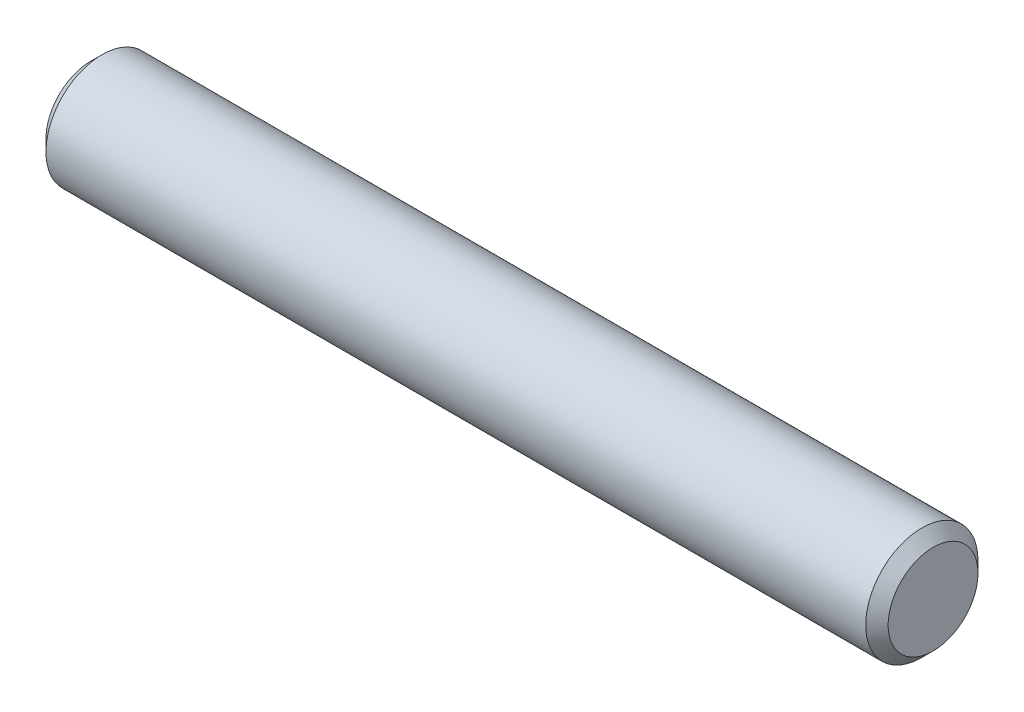
SolidWorks part; units mm, degrees
ref_plane "Front" through (0, 0, 0) normal (0, 0, 1) x (1, 0, 0)
ref_plane "Top" through (0, 0, 0) normal (0, 1, 0) x (1, 0, 0)
ref_plane "Right" through (0, 0, 0) normal (1, 0, 0) x (0, 0, -1)
sketch "Sketch1" plane through (0, 0, 0) normal (0, 0, 1) x (1, 0, 0)
  line L0 (-23.8125, 0) -> (23.8125, 0) construction
  line L1 (23.8125, 3.175) -> (23.8125, -3.175) construction
  line L2 (-23.8125, 3.175) -> (-23.8125, -3.175) construction
sketch "Sketch2" plane through (0, 0, 0) normal (1, 0, 0) x (0, 0, -1)
  line L0 (3.175, 0) -> (-3.175, 0) construction
  circle A0 centre (0, 0) radius 3.175
  point P6 (0, 0)
  dimension "D1" = 6.35
extrude "Extrude1" add sketch "Sketch2" against normal up to vertex (23.8125 mm away) and the other way up to vertex (23.8125 mm away) up to point (-23.8125, 3.175, 0) other way up to point (23.8125, 3.175, 0)
chamfer "Chamfer1" distance 0.635 angle 45 2 edges at (23.8125, 0, -3.175) (-23.8125, 0, -3.175)
ref_axis "Center Axis1" through (-12.2237, 0, 0) along (1, 0, 0)
ref_plane "Contact Plane1" through (-23.8125, 0, 0) normal (1, 0, 0) x (0, 0, -1)
ref_plane "Contact Plane2" through (23.8125, 0, 0) normal (1, 0, 0) x (0, 0, -1)
equation "\"D1@Chamfer1\" = \"Diameter@Sketch1\"*.1"
equation "\"D1@Sketch2\"=\"Diameter@Sketch1\""
